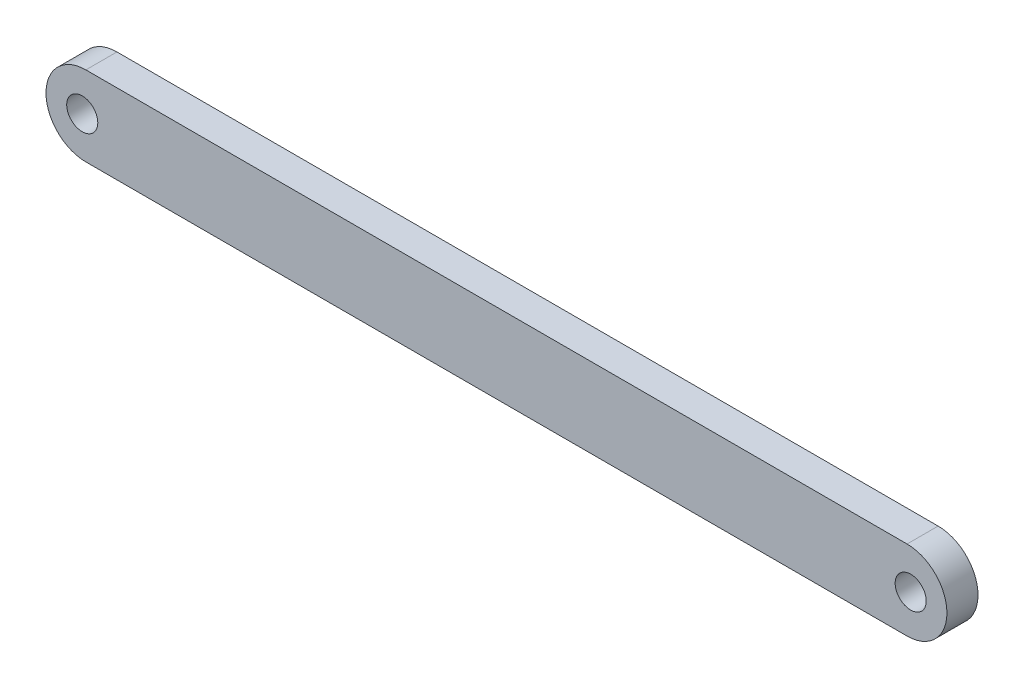
SolidWorks part; units mm, degrees
ref_plane "Plan de face" through (0, 0, 0) normal (0, 0, 1) x (1, 0, 0)
ref_plane "Plan de dessus" through (0, 0, 0) normal (0, 1, 0) x (1, 0, 0)
ref_plane "Plan de droite" through (0, 0, 0) normal (1, 0, 0) x (0, 0, -1)
sketch "Esquisse1" plane through (0, 0, 0) normal (0, 0, 1) x (1, 0, 0)
  line L0 (-87, 3.85) -> (0, 3.85) construction
  line L1 (0, 0) -> (-87, 0) construction
  line L2 (0, 0) -> (0, 7.7) construction
  line L3 (0, 7.7) -> (-87, 7.7) construction
  line L4 (-87, 0) -> (-87, 7.7) construction
  line L5 (-43.5, 7.7) -> (-43.5, 0) construction
  line L6 (-83.15, 7.7) -> (-3.85, 7.7)
  line L7 (-3.85, 0) -> (-83.15, 0)
  circle A0 centre (-3.5, 3.85) radius 1.5
  circle A1 centre (-83.5, 3.85) radius 1.5
  circle A2 centre (-83.15, 3.85) radius 3.85 construction
  circle A3 centre (-3.85, 3.85) radius 3.85 construction
  arc A4 (-83.15, 7.7) -> (-83.15, 0) centre (-83.15, 3.85) ccw
  arc A5 (-3.85, 7.7) -> (-3.85, 0) centre (-3.85, 3.85) cw
  dimension "D3" = 3
  dimension "D4" = 3
  dimension "D1" = 87
  dimension "D2" = 7.7
  dimension "D5" = 2
  dimension "D6" = 2
base flange "Tôle de base pliée1" sketch "Esquisse1" thickness 3 reverse thickness direction no parameters "D1"=1.5
sketch "Lignes de pliage1" [suppressed] plane through (0, 0, 0) normal (0, 1, 0) x (1, 0, 0)
sketch "Cube de visualisation1" [suppressed] plane through (0, 0, 0) normal (0, 1, 0) x (1, 0, 0)
sheet metal parameters "Tôlerie1" thickness 3 parameters "D1"=1.5
flat pattern "Etat déplié1" [suppressed]
sketch "Lignes de pliage2" plane through (0, 0, 0) normal (0, 1, 0) x (1, 0, 0)
sketch3d "Cube de visualisation2" [suppressed]
  line L0 (3.8497, -3.85, 0) -> (-83.1497, -3.85, 0) construction
  line L1 (3.8497, 3.85, 0) -> (-83.1497, 3.85, 0) construction
  line L2 (3.8497, -3.85, 0) -> (3.8497, 3.85, 0) construction
  line L3 (-83.1497, -3.85, 0) -> (-83.1497, 3.85, 0) construction
